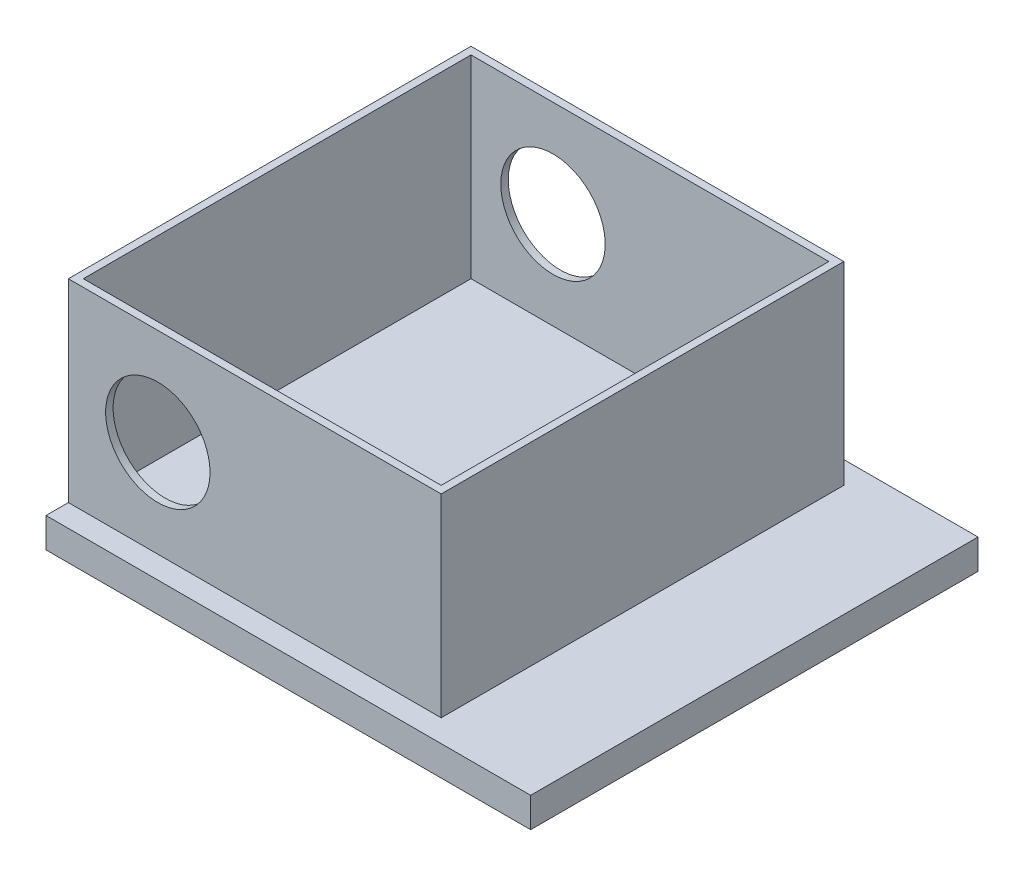
SolidWorks part; units mm, degrees
ref_plane "Plan de face" through (0, 0, 0) normal (0, 0, 1) x (1, 0, 0)
ref_plane "Plan de dessus" through (0, 0, 0) normal (0, 1, 0) x (1, 0, 0)
ref_plane "Plan de droite" through (0, 0, 0) normal (1, 0, 0) x (0, 0, -1)
sketch "Esquisse1" plane through (0, 0, 0) normal (0, 1, 0) x (1, 0, 0)
  line L0 (-20.4211, 23.2895) -> (4.0789, 23.2895)
  line L1 (4.0789, 23.2895) -> (4.0789, -2.7105)
  line L2 (4.0789, -2.7105) -> (-20.4211, -2.7105)
  line L3 (-20.4211, -2.7105) -> (-20.4211, 23.2895)
  line L4 (-20.4211, 23.2895) -> (-20.4211, 25.2895)
  line L5 (-20.4211, 25.2895) -> (12.0789, 25.2895)
  line L6 (12.0789, 25.2895) -> (12.0789, -4.7105)
  line L7 (12.0789, -4.7105) -> (-20.4211, -4.7105)
  line L8 (-20.4211, -4.7105) -> (-20.4211, -2.7105)
  line L9 (-20.4211, -2.7105) -> (-20.4211, -3.2105)
  line L10 (-20.4211, -3.2105) -> (4.5789, -3.2105)
  line L11 (4.5789, -3.2105) -> (4.5789, 23.7895)
  line L12 (4.5789, 23.7895) -> (-20.4211, 23.7895)
  line L13 (-19.9211, -2.7105) -> (-19.9211, 23.2895)
  line L14 (-15.9211, 23.2895) -> (-15.9211, 23.7895)
  line L15 (-8.9211, 23.2895) -> (-8.9211, 23.7895)
  line L16 (-8.9211, -3.2105) -> (-8.9211, -2.7105)
  line L17 (-15.9211, -2.7105) -> (-15.9211, -3.2105)
  point P14 (-15.9211, 23.2895)
  point P15 (-8.9211, 23.2895)
  point P20 (-15.9211, -2.7105)
  point P21 (-8.9211, -2.7105)
  dimension "D1" = 2
  dimension "D2" = 2
  dimension "D3" = 8
  dimension "D4" = 26
  dimension "D5" = 24
  dimension "D6" = 0.5
  dimension "D7" = 0.5
  dimension "D8" = 0.5
  dimension "D9" = 0.5
  dimension "D10" = 7
  dimension "4" = 4
  dimension "D11" = 4
  dimension "D12" = 7
extrude "Boss.-Extru.1" add sketch "Esquisse1" along normal blind 2 contours L3 L2 L1 L0 | L2 L13 L0 L3 | L2 L17 L10 L16 | L16 L10 L11 L12 L15 L0 L1 L2 | L0 L15 L12 L14 | L0 L14 L12 L4 | L17 L2 L8 L10 | L12 L11 L10 L8 L7 L6 L5 L4 region at (-18.1711, 0, -23.5395) region at (-20.1711, 0, -10.2895) region at (-7.9211, 0, -10.2895) region at (-18.1711, 0, 2.9605) region at (-19.9788, 0, -24.5395) region at (-12.4211, 0, -23.5395) region at (-8.6192, 0, -23.5395) region at (-12.4211, 0, 2.9605)
extrude "Boss.-Extru.2" add sketch "Esquisse1<4>" along normal blind 15 contours L11 L12 L4 L0 L1 L2 L8 L10 | L2 L13 L0 L3 | L0 L14 L12 L4 | L17 L2 L8 L10 | L2 L17 L10 L16 | L0 L15 L12 L14 region at (-18.1711, 0, -23.5395) region at (-20.1711, 0, -10.2895) region at (-18.1711, 0, 2.9605) region at (-12.4211, 0, -23.5395) region at (-8.6192, 0, -23.5395) region at (-12.4211, 0, 2.9605)
sketch "Esquisse1<4>" plane through (0, 0, 0) normal (0, 1, 0) x (1, 0, 0) same geometry as "Esquisse1"
sketch "Esquisse5" plane through (0, 0, -23.7895) normal (0, 0, -1) x (-1, 0, 0)
  line L0 (20.4211, 2) -> (-4.5789, 2) construction
  line L1 (20.4211, 2) -> (-12.0789, 2) construction
  line L2 (14.4211, 2) -> (14.4211, 8.5)
  circle A0 centre (14.4211, 8.5) radius 3.5
  point P0 (16.4211, 2)
  point P1 (14.4211, 2)
  dimension "D4" = 7
  dimension "D1" = 4
  dimension "D2" = 2
  dimension "D3" = 6.5
sketch "Esquisse6" plane through (0, 0, 3.2105) normal (0, 0, 1) x (1, 0, 0)
  circle A0 centre (-14.4211, 8.5) radius 3.5
  point P0 (-20.4211, 2)
  point P1 (-16.4211, 2)
  point P3 (-14.4211, 2)
  point P5 (-14.4211, 8.5)
  dimension "D1" = 7
extrude "Enlèv. mat.-Extru.2" cut sketch "Esquisse6" against normal blind 0.5
extrude "Enlèv. mat.-Extru.3" cut sketch "Esquisse5" against normal blind 0.5 contours A0
